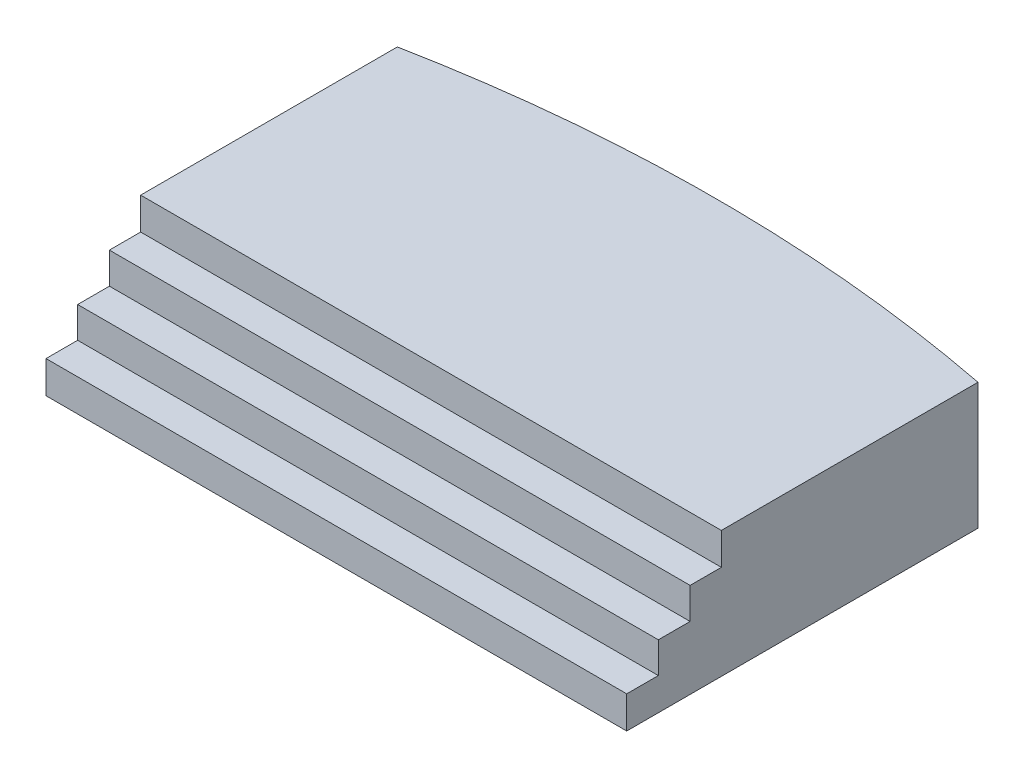
SolidWorks part; units mm, degrees
ref_plane "Front Plane" through (0, 0, 0) normal (0, 0, 1) x (1, 0, 0)
ref_plane "Top Plane" through (0, 0, 0) normal (0, 1, 0) x (1, 0, 0)
ref_plane "Right Plane" through (0, 0, 0) normal (1, 0, 0) x (0, 0, -1)
sketch "Sketch1" plane through (0, 0, 0) normal (0, 1, 0) x (1, 0, 0)
  line L0 (0, 12000) -> (0, 6000) construction
  line L1 (-4067.1162, 9000) -> (3864.1234, 9000)
  line L3 (-4067.1162, 9000) -> (-4067.1162, 11289.7549)
  line L4 (3864.1234, 9000) -> (3864.1234, 11360.8341)
  arc A1 (0, 12000) -> (-4067.1162, 11289.7549) centre (0, 0) ccw
  arc A2 (0, 12000) -> (3864.1234, 11360.8341) centre (0, 0) cw
extrude "Boss-Extrude1" add sketch "Sketch1" along normal blind 1000 contours A2 L4 L1 L3 A1
sketch "Sketch2" plane through (3864.1234, 0, 0) normal (1, 0, 0) x (0, 0, -1)
  line L1 (9000, 1000) -> (9000, 0) construction
  line L2 (9000, 254.9104) -> (9250.2457, 254.9104)
  line L3 (9250.2457, 254.9104) -> (9250.2457, 500)
  line L4 (9250.2457, 500) -> (9501.4119, 500)
  line L5 (9501.4119, 500) -> (9501.4119, 747.1151)
  line L6 (9501.4119, 747.1151) -> (9748.527, 747.1151)
  line L7 (9748.527, 747.1151) -> (9748.527, 1000)
  line L8 (9000, 1000) -> (11360.8341, 1000) construction
  line L9 (9748.527, 1000) -> (9000, 1000)
  line L10 (9000, 1000) -> (9000, 254.9104)
extrude "Cut-Extrude1" cut sketch "Sketch2" against normal blind 24000
sketch "Sketch3" plane through (0, 1000, 0) normal (0, 1, 0) x (1, 0, 0)
  line L0 (0, 9000) -> (0, 12000) construction
  line L1 (-4067.1162, 11289.7549) -> (3864.1234, 11289.7549)
  line L2 (-4067.1162, 11289.7549) -> (-4067.1162, 9000)
  line L3 (-4067.1162, 9000) -> (3864.1234, 9000)
  line L4 (3864.1234, 11289.7549) -> (3864.1234, 9000)
  line L5 (3864.1234, 11289.7549) -> (4067.1162, 11289.7549)
  line L6 (4067.1162, 11289.7549) -> (4067.1162, 9000)
  arc A1 (4067.1162, 11289.7549) -> (-4067.1162, 11289.7549) centre (0, 0) ccw
sketch "Sketch4" plane through (3864.1234, 0, 0) normal (1, 0, 0) x (0, 0, -1)
  line L0 (9000, 254.9104) -> (9000, 0)
  line L1 (9000, 0) -> (11360.8341, 0)
  line L2 (11360.8341, 0) -> (11360.8341, 1000)
  line L3 (11360.8341, 1000) -> (9748.527, 1000)
  line L4 (9748.527, 1000) -> (9748.527, 747.1151)
  line L5 (9748.527, 747.1151) -> (9501.4119, 747.1151)
  line L6 (9501.4119, 747.1151) -> (9501.4119, 500)
  line L7 (9501.4119, 500) -> (9250.2457, 500)
  line L8 (9250.2457, 500) -> (9250.2457, 254.9104)
  line L9 (9250.2457, 254.9104) -> (9000, 254.9104)
extrude "Boss-Extrude2" add sketch "Sketch4" along normal blind 202.9928
sketch "Sketch5" plane through (0, 1000, 0) normal (0, 1, 0) x (1, 0, 0)
  line L0 (4067.1162, 11289.7549) -> (4067.1162, 11360.8341)
  line L1 (4067.1162, 11360.8341) -> (3864.1234, 11360.8341)
  line L3 (0, 12000) -> (0, 9000) construction
  line L4 (-4067.1162, 9000) -> (4067.1162, 9000) construction
  line L5 (4067.1162, 11289.7549) -> (4067.1162, 9748.527)
  line L6 (4067.1162, 9748.527) -> (0, 9748.527)
  line L7 (-4067.1162, 9748.527) -> (4067.1162, 9748.527) construction
  arc A0 (3864.1234, 11360.8341) -> (-4067.1162, 11289.7549) centre (0, 0) ccw construction
  arc A1 (3864.1234, 11360.8341) -> (4067.1162, 11289.7549) centre (0, 0) cw
extrude "Cut-Extrude5" cut sketch "Sketch5" against normal blind 4000 contours L0 L1 A1
sketch "Sketch9" plane through (0, 0, 0) normal (0, -1, 0) x (1, 0, 0)
  line L0 (0, -9000) -> (0, -12000) construction
  line L1 (-4067.1162, -9000) -> (4067.1162, -9000) construction
  line L7 (2296.3939, -12199.1971) -> (4067.1162, -12199.1971)
  line L8 (4067.1162, -9000) -> (4067.1162, -12199.1971)
  line L9 (2296.3939, -9000) -> (4067.1162, -9000)
  line L10 (-2296.3939, -9000) -> (-4067.1162, -9000)
  line L12 (-2296.3939, -12199.1971) -> (-4067.1162, -12199.1971)
  line L13 (-4067.1162, -9000) -> (-4067.1162, -12199.1971)
  line L14 (-2296.3939, -12199.1971) -> (-2296.3939, -9000)
  line L15 (2296.3939, -12199.1971) -> (2296.3939, -9000)
  arc A0 (-4067.1162, -11289.7549) -> (4067.1162, -11289.7549) centre (0, 0) ccw construction
  dimension "D1" = 3000
extrude "Cut-Extrude6" cut sketch "Sketch9" against normal blind 2000 and the other way blind 2000
